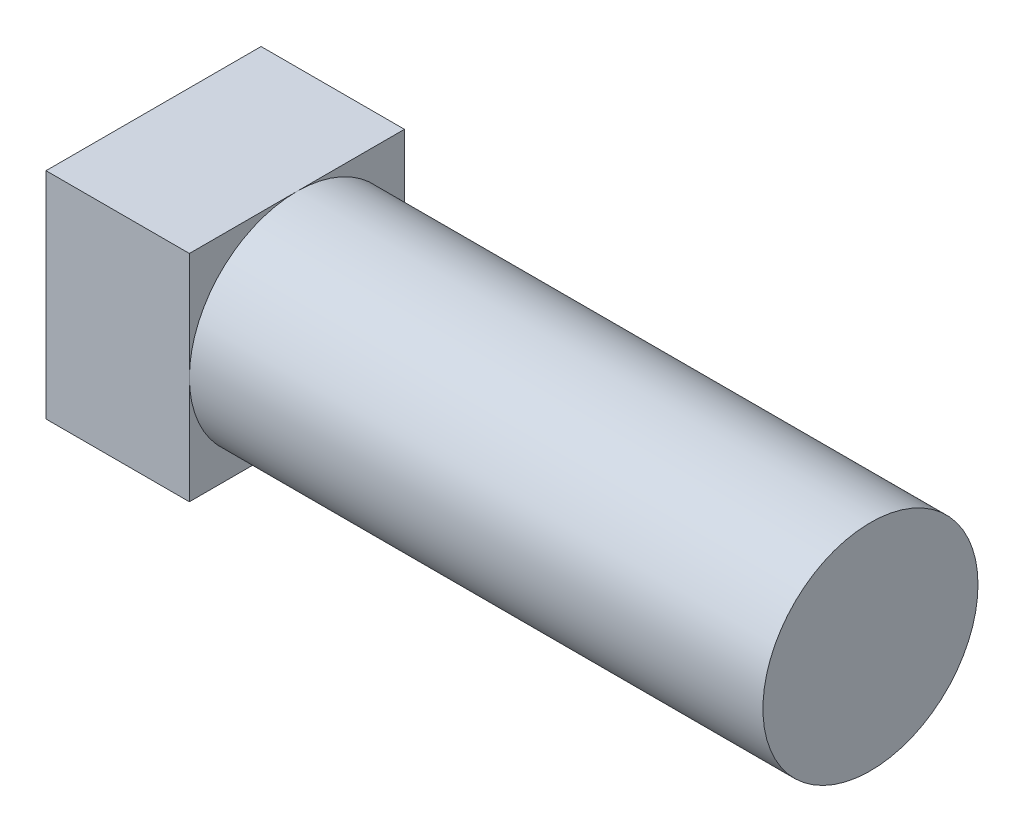
SolidWorks part; units mm, degrees
ref_plane "Front Plane" through (0, 0, 0) normal (0, 0, 1) x (1, 0, 0)
ref_plane "Top Plane" through (0, 0, 0) normal (0, 1, 0) x (1, 0, 0)
ref_plane "Right Plane" through (0, 0, 0) normal (1, 0, 0) x (0, 0, -1)
sketch "Sketch1" plane through (0, 0, 0) normal (1, 0, 0) x (0, 0, -1)
  line L1 (-7.5, 7.5) -> (7.5, 7.5)
  line L2 (-7.5, 7.5) -> (-7.5, -7.5)
  line L3 (-7.5, -7.5) -> (7.5, -7.5)
  line L4 (7.5, 7.5) -> (7.5, -7.5)
  line L5 (-7.5, 7.5) -> (7.5, -7.5) construction
  line L6 (-7.5, -7.5) -> (7.5, 7.5) construction
  point P0 (0, 0)
  dimension "D1" = 15
  dimension "D2" = 15
extrude "Boss-Extrude1" add sketch "Sketch1" along normal blind 10
sketch "Sketch2" plane through (10, 0, 0) normal (1, 0, 0) x (0, 0, -1)
  circle A0 centre (0, 0) radius 7.5
extrude "Boss-Extrude2" add sketch "Sketch2" along normal blind 40
